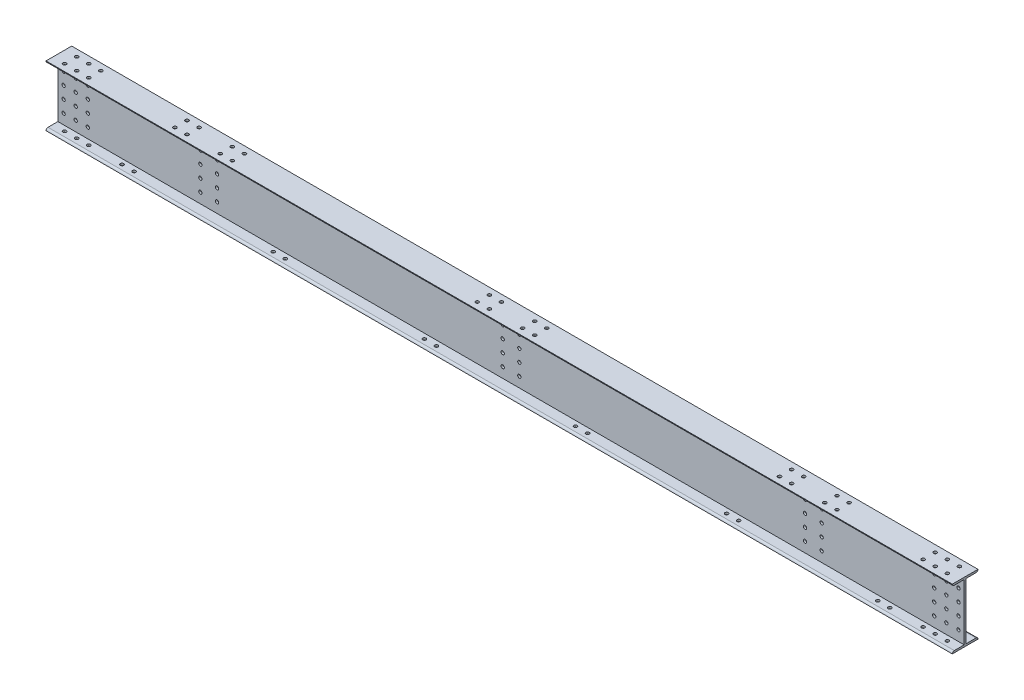
SolidWorks part; units mm, degrees
ref_plane "前视基准面" through (0, 0, 0) normal (0, 0, 1) x (1, 0, 0)
ref_plane "上视基准面" through (0, 0, 0) normal (0, 1, 0) x (1, 0, 0)
ref_plane "右视基准面" through (0, 0, 0) normal (1, 0, 0) x (0, 0, -1)
sketch "草图1" plane through (0, 0, 0) normal (0, 0, 1) x (1, 0, 0)
  line L1 (0, 400) -> (5996, 400)
  line L2 (0, 400) -> (0, 0)
  line L3 (0, 0) -> (5996, 0)
  line L4 (5996, 400) -> (5996, 0)
  dimension "D1" = 5996
  dimension "D2" = 400
extrude "拉伸1" add sketch "草图1" along normal blind 170
sketch "草图2" plane through (0, 0, 170) normal (0, 0, 1) x (1, 0, 0)
  line L0 (0, 0) -> (5996, 0) construction
  line L1 (0, 400) -> (0, 0) construction
  circle A0 centre (38, 80) radius 11
  dimension "D1" = 80
  dimension "D2" = 38
extrude "切除-拉伸2" cut sketch "草图2" against normal through all
pattern_linear "阵列(线性)4" count 4 spacing 80 along (0, 1, 0) of "切除-拉伸2"
pattern_linear "阵列(线性)5" count 2 spacing 80 along (1, 0, 0) of "切除-拉伸2", "阵列(线性)4"
pattern_linear "阵列(线性)6" count 2 spacing 160 along (1, 0, 0) of "切除-拉伸2", "阵列(线性)4"
pattern_linear "阵列(线性)7" count 2 spacing 905 along (1, 0, 0) of "切除-拉伸2", "阵列(线性)4"
pattern_linear "阵列(线性)8" count 2 spacing 2905 along (1, 0, 0) of "切除-拉伸2", "阵列(线性)4"
pattern_linear "阵列(线性)9" count 2 spacing 4905 along (1, 0, 0) of "切除-拉伸2", "阵列(线性)4"
pattern_linear "阵列(线性)10" count 2 spacing 5760 along (1, 0, 0) of "切除-拉伸2", "阵列(线性)4", "阵列(线性)5", "阵列(线性)6"
pattern_linear "阵列(线性)37" count 2 spacing 3015 along (1, 0, 0) of "切除-拉伸2", "阵列(线性)4"
pattern_linear "阵列(线性)40" count 2 spacing 1015 along (1, 0, 0) of "切除-拉伸2", "阵列(线性)4"
pattern_linear "阵列(线性)41" count 2 spacing 5015 along (1, 0, 0) of "切除-拉伸2", "阵列(线性)4"
sketch "草图3" plane through (0, 400, 0) normal (0, 1, 0) x (1, 0, 0)
  line L1 (0, -170) -> (0, 0) construction
  circle A0 centre (78, -125) radius 11
  point P2 (0, -85)
  dimension "D1" = 40
  dimension "D2" = 78
extrude "切除-拉伸3" cut sketch "草图3" against normal blind 120
pattern_linear "阵列(线性)11" count 2 spacing 80 along (0, 0, -1) of "切除-拉伸3"
pattern_linear "阵列(线性)12" count 2 spacing 80 along (1, 0, 0) of "切除-拉伸3", "阵列(线性)11"
pattern_linear "阵列(线性)13" count 2 spacing 160 along (1, 0, 0) of "切除-拉伸3", "阵列(线性)11"
pattern_linear "阵列(线性)14" count 2 spacing 730 along (1, 0, 0) of "切除-拉伸3", "阵列(线性)11", "阵列(线性)12"
pattern_linear "阵列(线性)16" count 2 spacing 1030 along (1, 0, 0) of "切除-拉伸3", "阵列(线性)11", "阵列(线性)12"
pattern_linear "阵列(线性)17" count 2 spacing 2730 along (1, 0, 0) of "切除-拉伸3", "阵列(线性)11", "阵列(线性)12"
pattern_linear "阵列(线性)19" count 2 spacing 3030 along (1, 0, 0) of "切除-拉伸3", "阵列(线性)11", "阵列(线性)12"
pattern_linear "阵列(线性)20" count 2 spacing 4730 along (1, 0, 0) of "切除-拉伸3", "阵列(线性)11", "阵列(线性)12"
pattern_linear "阵列(线性)22" count 2 spacing 5030 along (1, 0, 0) of "切除-拉伸3", "阵列(线性)11", "阵列(线性)12"
pattern_linear "阵列(线性)23" count 2 spacing 5680 along (1, 0, 0) of "切除-拉伸3", "阵列(线性)11", "阵列(线性)12", "阵列(线性)13"
sketch "草图4" plane through (0, 0, 0) normal (0, -1, 0) x (1, 0, 0)
  line L0 (0, 170) -> (0, 0) construction
  line L1 (0, 170) -> (0, 0) construction
  circle A0 centre (78, 45) radius 11
  point P2 (0, 85)
  dimension "D1" = 40
  dimension "D2" = 78
extrude "切除-拉伸4" cut sketch "草图4" against normal blind 120
pattern_linear "阵列(线性)24" count 2 spacing 80 along (0, 0, 1) of "切除-拉伸4"
pattern_linear "阵列(线性)25" count 2 spacing 80 along (1, 0, 0) of "切除-拉伸4", "阵列(线性)24"
pattern_linear "阵列(线性)26" count 2 spacing 160 along (1, 0, 0) of "切除-拉伸4", "阵列(线性)24"
pattern_linear "阵列(线性)27" count 2 spacing 380 along (1, 0, 0) of "切除-拉伸4", "阵列(线性)24", "阵列(线性)25"
pattern_linear "阵列(线性)28" count 2 spacing 1380 along (1, 0, 0) of "切除-拉伸4", "阵列(线性)24", "阵列(线性)25"
pattern_linear "阵列(线性)29" count 2 spacing 2380 along (1, 0, 0) of "切除-拉伸4", "阵列(线性)24", "阵列(线性)25"
pattern_linear "阵列(线性)30" count 2 spacing 3380 along (1, 0, 0) of "切除-拉伸4", "阵列(线性)24", "阵列(线性)25"
pattern_linear "阵列(线性)31" count 2 spacing 4380 along (1, 0, 0) of "切除-拉伸4", "阵列(线性)24", "阵列(线性)25"
pattern_linear "阵列(线性)32" count 2 spacing 5380 along (1, 0, 0) of "切除-拉伸4", "阵列(线性)24", "阵列(线性)25"
pattern_linear "阵列(线性)33" count 2 spacing 5680 along (1, 0, 0) of "切除-拉伸4", "阵列(线性)24", "阵列(线性)25", "阵列(线性)26"
sketch "草图6" plane through (0, 0, 0) normal (-1, 0, 0) x (0, 0, 1)
  line L0 (170, 400) -> (0, 400) construction
  line L1 (0, 400) -> (0, 0) construction
  line L2 (0, 387) -> (78.5, 387)
  line L3 (0, 387) -> (0, 13)
  line L4 (0, 13) -> (78.5, 13)
  line L5 (78.5, 387) -> (78.5, 13)
  line L6 (170, 400) -> (170, 0) construction
  line L7 (170, 387) -> (91.5, 387)
  line L8 (170, 387) -> (170, 13)
  line L9 (170, 13) -> (91.5, 13)
  line L10 (91.5, 387) -> (91.5, 13)
  line L11 (170, 0) -> (0, 0) construction
  line L12 (170, 400) -> (0, 400) construction
  point P0 (85, 400)
  dimension "D1" = 13
  dimension "D2" = 6.5
  dimension "D3" = 13
extrude "切除-拉伸5" cut sketch "草图6" against normal through all
fillet "圆角1" radius 13 1 edges at (2998, 387, 170)
fillet "圆角2" radius 13 1 edges at (2998, 13, 170)
fillet "圆角3" radius 13 1 edges at (2998, 13, 0)
fillet "圆角4" radius 13 1 edges at (2998, 387, 0)
